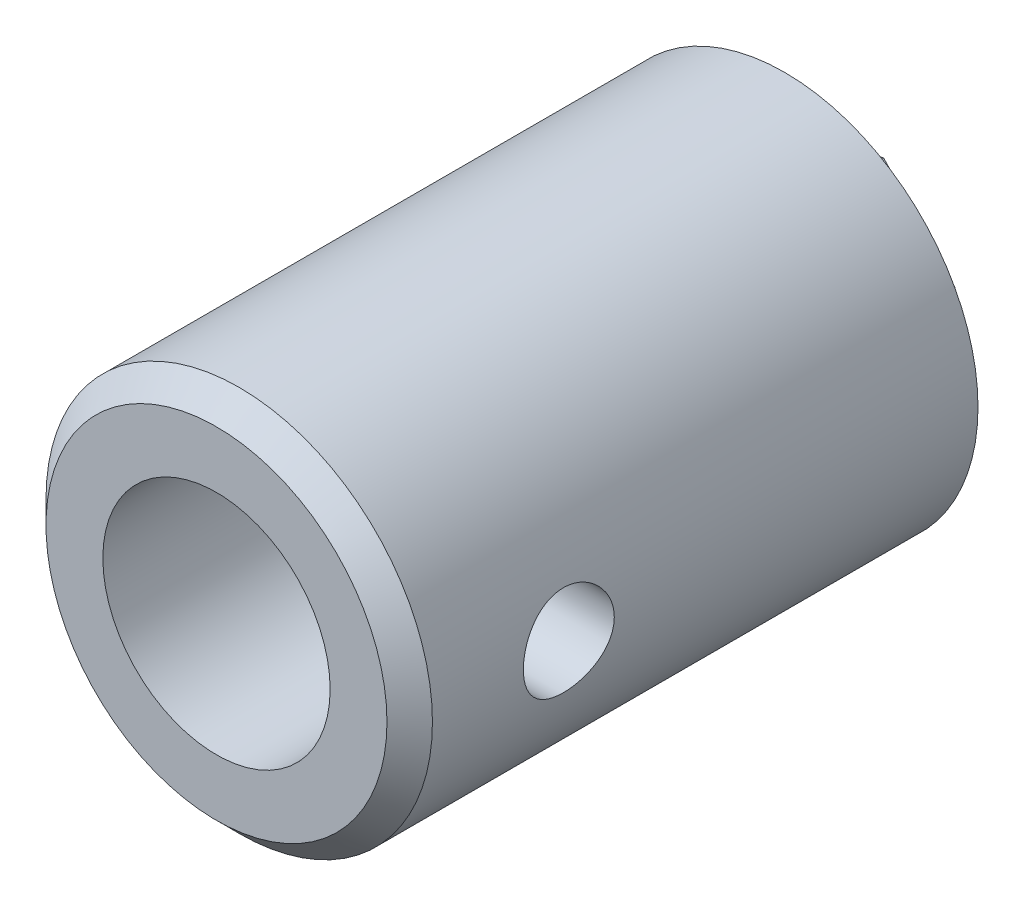
SolidWorks part; units mm, degrees
ref_plane "Front Plane" through (0, 0, 0) normal (0, 0, 1) x (1, 0, 0)
ref_plane "Top Plane" through (0, 0, 0) normal (0, 1, 0) x (1, 0, 0)
ref_plane "Right Plane" through (0, 0, 0) normal (1, 0, 0) x (0, 0, -1)
sketch "Sketch1" plane through (0, 0, 0) normal (0, 0, 1) x (1, 0, 0)
  circle A0 centre (0, 0) radius 8.5
  circle A1 centre (0, 0) radius 2
  dimension "D1" = 17
  dimension "D2" = 4
extrude "Boss-Extrude1" add sketch "Sketch1" along normal blind 5 contours A0 | A1
sketch "Sketch2" plane through (0, 0, 5) normal (0, 0, 1) x (1, 0, 0)
  circle A0 centre (0, 0) radius 8.5
  circle A1 centre (0, 0) radius 5
  circle M1 centre (0, 0) radius 8.5
  dimension "D1" = 10
extrude "Boss-Extrude2" add sketch "Sketch2" along normal blind 20 contours A1 M1 region at (-8.2596, 0, 5)
sketch "Sketch3" plane through (0, 0, 0) normal (0, 0, -1) x (-1, 0, 0)
  line L1 (-4.5006, 1.0383) -> (-3.1495, -3.3785)
  line L2 (-3.1495, -3.3785) -> (1.3511, -4.4168)
  line L3 (1.3511, -4.4168) -> (4.5006, -1.0383)
  line L4 (4.5006, -1.0383) -> (3.1495, 3.3785)
  line L5 (3.1495, 3.3785) -> (-1.3511, 4.4168)
  line L6 (-1.3511, 4.4168) -> (-4.5006, 1.0383)
  circle A0 centre (0, 0) radius 4 construction
  circle A1 centre (0, 0) radius 2
  circle A2 centre (0, 0) radius 2 construction
  dimension "D1" = 8
extrude "Boss-Extrude3" add sketch "Sketch3" along normal blind 3
chamfer "Chamfer1" distance 1 angle 45 1 edges at (8.5, 0, 25)
ref_plane "Plane1" through (8.5, 0, 0) normal (1, 0, 0) x (0, 0, -1)
sketch "Sketch4" plane through (8.5, 0, 0) normal (1, 0, 0) x (0, 0, -1)
  line L0 (0, -8.5) -> (0, 8.5) construction
  circle A0 centre (-18, 0) radius 2
  dimension "D1" = 4
  dimension "D2" = 18
extrude "Cut-Extrude1" cut sketch "Sketch4" against normal up to next contours A0
